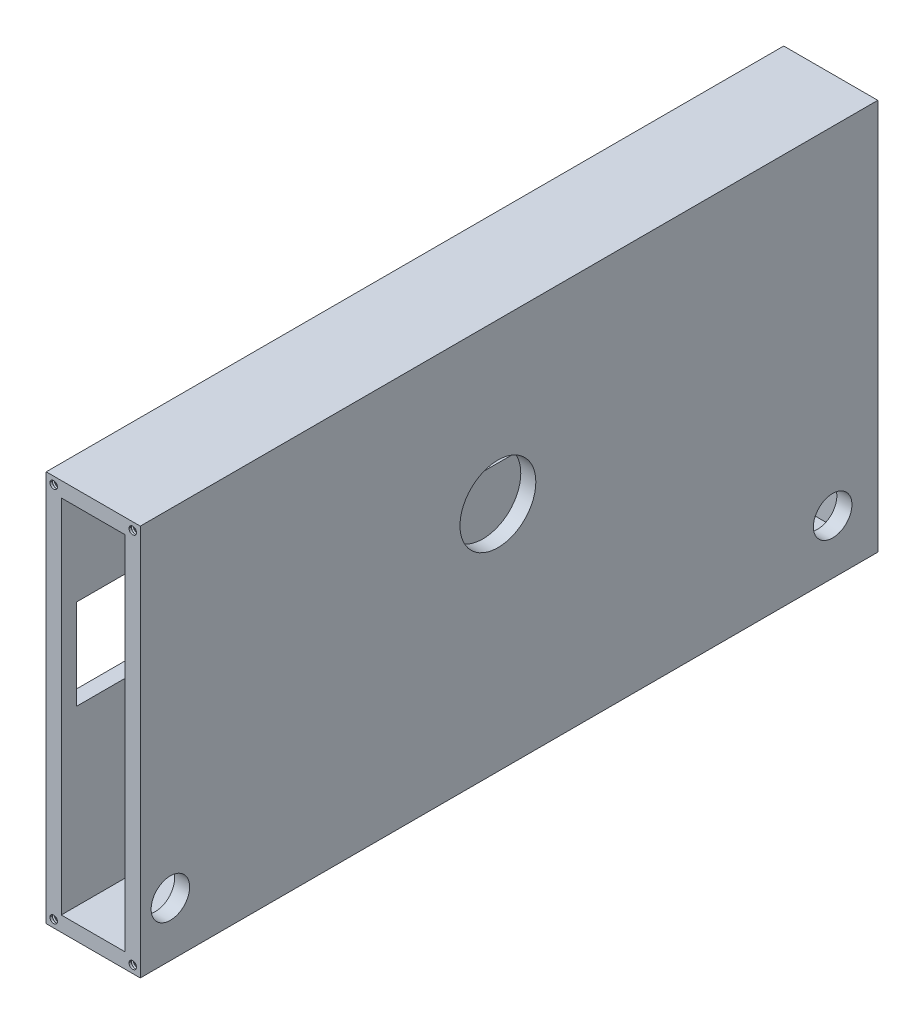
SolidWorks part; units mm, degrees
ref_plane "Front Plane" through (0, 0, 0) normal (0, 0, 1) x (1, 0, 0)
ref_plane "Top Plane" through (0, 0, 0) normal (0, 1, 0) x (1, 0, 0)
ref_plane "Right Plane" through (0, 0, 0) normal (1, 0, 0) x (0, 0, -1)
sketch "Sketch1" plane through (0, 0, 0) normal (0, 0, 1) x (1, 0, 0)
  line L1 (0, 0) -> (39.6875, 0)
  line L2 (0, 0) -> (0, 165.1)
  line L3 (0, 165.1) -> (39.6875, 165.1)
  line L4 (39.6875, 0) -> (39.6875, 165.1)
  dimension "D1" = 39.6875
  dimension "D2" = 165.1
extrude "Boss-Extrude1" add sketch "Sketch1" against normal blind 311.15
shell "Shell1" thickness 6.35 removed face at (19.8438, 82.55, 0)
sketch "Sketch2" plane through (39.6875, 0, 0) normal (1, 0, 0) x (0, 0, -1)
  line L0 (311.15, 0) -> (0, 0) construction
  line L1 (311.15, 0) -> (311.15, 165.1) construction
  circle A1 centre (12.7, 22.86) radius 8.128
  circle A2 centre (292.1, 22.86) radius 8.128
  dimension "D6" = 16.256
  dimension "D9" = 16.256
  dimension "D4" = 22.86
  dimension "D5" = 12.7
  dimension "D7" = 19.05
  dimension "D8" = 22.86
extrude "Cut-Extrude2" cut sketch "Sketch2" against normal blind 12.7
sketch "Sketch4" plane through (39.6875, 0, 0) normal (1, 0, 0) x (0, 0, -1)
  line L6 (0, 0) -> (0, 165.1) construction
  line L7 (6.35, 117.475) -> (304.8, 117.475)
  line L8 (6.35, 117.475) -> (6.35, 79.375)
  line L9 (6.35, 79.375) -> (304.8, 79.375)
  line L10 (304.8, 117.475) -> (304.8, 79.375)
  line L11 (311.15, 0) -> (311.15, 165.1) construction
  dimension "D1" = 38.1
  dimension "D2" = 79.375
  dimension "D3" = 6.35
  dimension "D4" = 6.35
sketch "Sketch5" plane through (0, 0, 0) normal (0, 0, 1) x (1, 0, 0)
  line L0 (39.6875, 0) -> (39.6875, 165.1) construction
  line L1 (0, 0) -> (39.6875, 0) construction
  line L2 (0, 165.1) -> (0, 0) construction
  circle A0 centre (3.175, 161.925) radius 1.5875
  circle A1 centre (36.5125, 161.925) radius 1.5875
  circle A2 centre (3.175, 3.175) radius 1.5875
  circle A3 centre (36.5125, 3.175) radius 1.5875
  dimension "D1" = 3.175
  dimension "D4" = 3.175
  dimension "D7" = 3.175
  dimension "D10" = 3.175
  dimension "D2" = 3.175
  dimension "D3" = 3.175
  dimension "D5" = 3.175
  dimension "D6" = 3.175
  dimension "D8" = 3.175
  dimension "D9" = 3.175
  dimension "D11" = 3.175
  dimension "D12" = 3.175
extrude "Cut-Extrude6" cut sketch "Sketch5" against normal blind 6.35
thread "Thread1" pitch 1.0583 method cut profile "Thread Profile1" start angle 0, offset 0, length 0, pitch 1.0583, diameter 3.175
ref_plane "Plane2" through (1.5875, 161.925, 0) normal (0, -1, 0) x (-1, 0, 0)
sketch "Thread Profile1" plane through (1.5875, 161.925, 0) normal (0, -1, 0) x (-1, 0, 0)
  line L0 (0, 0) -> (0, 1.0583) construction
  line L1 (0, 0) -> (0.5728, 0.3307)
  line L2 (0.5728, 0.3307) -> (0.5728, 0.463)
  line L3 (0.5728, 0.463) -> (0, 0.7937)
  line L4 (0.5728, 0.3969) -> (0, 0.3969) construction
  line L11 (0, 0) -> (0, 0.7937)
  point P2 (0, 0)
  dimension "Pitch" = 1.0583
  dimension "Profile_Angle" = 60
  dimension "Profile_Land" = 0.1323
  dimension "Profile_Height" = 0.5728
thread "Thread2" pitch 1.0583 method cut profile "Thread Profile2" start angle 0, offset 0, length 0, pitch 1.0583, diameter 3.175
ref_plane "Plane3" through (34.925, 161.925, 0) normal (0, -1, 0) x (-1, 0, 0)
sketch "Thread Profile2" plane through (34.925, 161.925, 0) normal (0, -1, 0) x (-1, 0, 0)
  line L0 (0, 0) -> (0, 1.0583) construction
  line L1 (0, 0) -> (0.5728, 0.3307)
  line L2 (0.5728, 0.3307) -> (0.5728, 0.463)
  line L3 (0.5728, 0.463) -> (0, 0.7937)
  line L4 (0.5728, 0.3969) -> (0, 0.3969) construction
  line L11 (0, 0) -> (0, 0.7937)
  point P2 (0, 0)
  dimension "Pitch" = 1.0583
  dimension "Profile_Angle" = 60
  dimension "Profile_Land" = 0.1323
  dimension "Profile_Height" = 0.5728
thread "Thread3" pitch 1.0583 method cut profile "Thread Profile3" start angle 0, offset 0, length 0, pitch 1.0583, diameter 3.175
ref_plane "Plane4" through (1.5875, 3.175, 0) normal (0, -1, 0) x (-1, 0, 0)
sketch "Thread Profile3" plane through (1.5875, 3.175, 0) normal (0, -1, 0) x (-1, 0, 0)
  line L0 (0, 0) -> (0, 1.0583) construction
  line L1 (0, 0) -> (0.5728, 0.3307)
  line L2 (0.5728, 0.3307) -> (0.5728, 0.463)
  line L3 (0.5728, 0.463) -> (0, 0.7937)
  line L4 (0.5728, 0.3969) -> (0, 0.3969) construction
  line L11 (0, 0) -> (0, 0.7937)
  point P2 (0, 0)
  dimension "Pitch" = 1.0583
  dimension "Profile_Angle" = 60
  dimension "Profile_Land" = 0.1323
  dimension "Profile_Height" = 0.5728
thread "Thread4" pitch 1.0583 method cut profile "Thread Profile4" start angle 0, offset 0, length 0, pitch 1.0583, diameter 3.175
ref_plane "Plane5" through (34.925, 3.175, 0) normal (0, -1, 0) x (-1, 0, 0)
sketch "Thread Profile4" plane through (34.925, 3.175, 0) normal (0, -1, 0) x (-1, 0, 0)
  line L0 (0, 0) -> (0, 1.0583) construction
  line L1 (0, 0) -> (0.5728, 0.3307)
  line L2 (0.5728, 0.3307) -> (0.5728, 0.463)
  line L3 (0.5728, 0.463) -> (0, 0.7937)
  line L4 (0.5728, 0.3969) -> (0, 0.3969) construction
  line L11 (0, 0) -> (0, 0.7937)
  point P2 (0, 0)
  dimension "Pitch" = 1.0583
  dimension "Profile_Angle" = 60
  dimension "Profile_Land" = 0.1323
  dimension "Profile_Height" = 0.5728
sketch "Sketch14" plane through (0, 0, 0) normal (-1, 0, 0) x (0, 0, 1)
  line L1 (-304.8, 117.475) -> (-6.35, 117.475)
  line L2 (-304.8, 117.475) -> (-304.8, 79.375)
  line L3 (-304.8, 79.375) -> (-6.35, 79.375)
  line L4 (-6.35, 117.475) -> (-6.35, 79.375)
extrude "Cut-Extrude7" cut sketch "Sketch14" against normal blind 6.35
sketch "Sketch15" plane through (39.6875, 0, 0) normal (1, 0, 0) x (0, 0, -1)
  line L0 (311.15, 0) -> (0, 0) construction
  line L1 (0, 0) -> (0, 165.1) construction
  circle A0 centre (150.876, 97.79) radius 16.002
  dimension "D1" = 32.004
  dimension "D2" = 97.79
  dimension "D3" = 150.876
extrude "Cut-Extrude8" cut sketch "Sketch15" against normal blind 12.7
